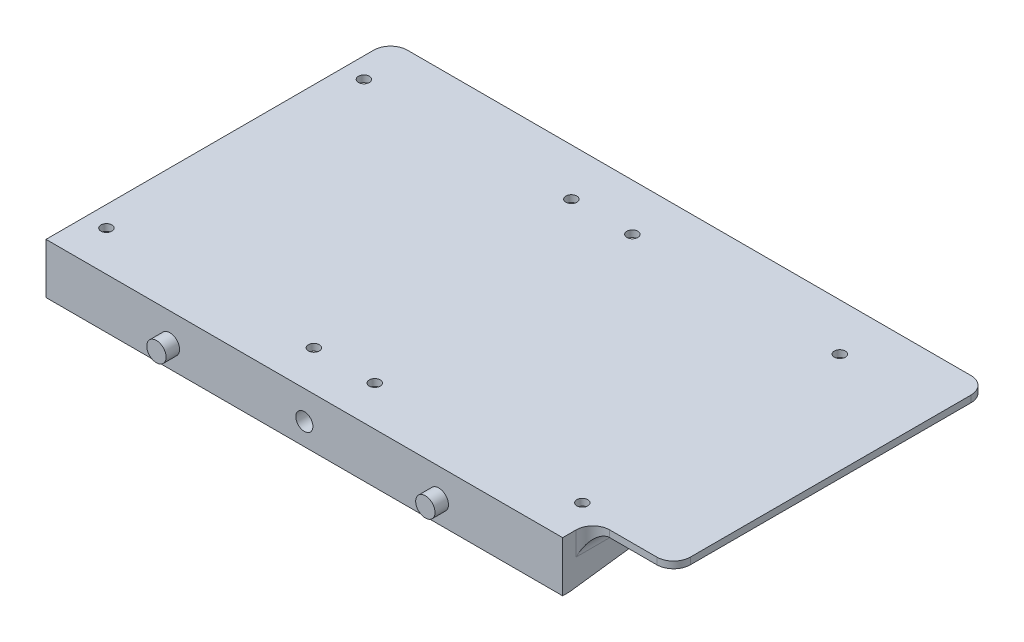
SolidWorks part; units mm, degrees
ref_plane "Front Plane" through (0, 0, 0) normal (0, 0, 1) x (1, 0, 0)
ref_plane "Top Plane" through (0, 0, 0) normal (0, 1, 0) x (1, 0, 0)
ref_plane "Right Plane" through (0, 0, 0) normal (1, 0, 0) x (0, 0, -1)
sketch "Sketch1" plane through (0, 0, 0) normal (0, 1, 0) x (1, 0, 0)
  line L0 (69.85, 0) -> (79.85, 0)
  line L1 (0, 0) -> (69.85, 0)
  line L2 (0, 0) -> (0, 100.5)
  line L3 (0, 100.5) -> (69.85, 100.5)
  line L4 (69.85, 0) -> (69.85, 100.5)
  line L5 (69.85, 100.5) -> (79.85, 100.5)
  line L6 (79.85, 0) -> (149.7, 0)
  line L7 (79.85, 0) -> (79.85, 100.5)
  line L8 (79.85, 100.5) -> (149.7, 100.5)
  line L9 (149.7, 0) -> (149.7, 100.5)
  line L10 (0, 100.5) -> (0, 86.5)
  line L11 (0, 86.5) -> (4.07, 86.5)
  line L12 (4.07, 86.5) -> (65.79, 86.5)
  line L13 (65.79, 86.5) -> (65.79, 9.9)
  line L14 (65.79, 9.9) -> (4.07, 9.9)
  circle A0 centre (4.07, 86.5) radius 1.625
  circle A1 centre (4.07, 9.9) radius 1.625
  circle A2 centre (65.79, 9.9) radius 1.625
  circle A3 centre (65.79, 86.5) radius 1.625
  circle A4 centre (145.64, 9.9) radius 1.625
  circle A5 centre (83.92, 9.9) radius 1.625
  circle A6 centre (83.92, 86.5) radius 1.625
  circle A7 centre (145.64, 86.5) radius 1.625
extrude "Boss-Extrude1" add sketch "Sketch1" along normal blind 2 contours A3 A2 A1 A0 L2 L1 L4 L3 | L0 L7 L5 L4 | L6 L9 L8 L7 A7 A6 A5 A4 region at (74.85, 0, -50.25) region at (34.925, 0, -50.2597) region at (114.775, 0, -50.2597)
ref_plane "Plane1" through (149.7, 0, 0) normal (1, 0, 0) x (0, 0, -1)
sketch "Sketch3" plane through (0, 0, 0) normal (0, 0, 1) x (1, 0, 0)
  line L0 (0, 2) -> (149.7, 2)
  line L1 (149.7, -41.1675) -> (149.7, 41.1675) construction
  line L2 (0, 2) -> (149.7, 2) construction
  line L3 (149.7, 2) -> (159.7, 2)
  line L4 (159.7, 2) -> (159.7, -13)
  line L5 (0, 2) -> (-10, 2)
  line L6 (-10, 2) -> (-10, -13)
  line L8 (-10, 2) -> (159.7, 2)
  line L9 (-10, 2) -> (-10, -13)
  line L10 (-10, -13) -> (159.7, -13)
  line L11 (159.7, 2) -> (159.7, -13)
  line M5 (0, 0) -> (149.7, 0)
  line M6 (149.7, 0) -> (149.7, 2)
  line M7 (149.7, 2) -> (0, 2)
  line M8 (0, 2) -> (0, 0)
extrude "Boss-Extrude2" add sketch "Sketch3" along normal blind 2 contours L6 L10 L4 L3 L5 M6 M5 M8 | M8 M5 M6 M7 region at (74.85, -6.3664, 0) region at (74.85, 1, 0)
sketch "Sketch4" plane through (0, 0, 0) normal (-1, 0, 0) x (0, 0, 1)
  line L0 (-100.5, 0) -> (0, -13)
  line L1 (0, -13) -> (0, 2)
  line L2 (0, 2) -> (-100.5, 2)
  line L7 (-100.5, 0) -> (0, 0)
  line L8 (0, 0) -> (0, 2)
  line L9 (0, 2) -> (-100.5, 2)
  line L10 (-100.5, 2) -> (-100.5, 0)
  line L11 (-100.5, 0) -> (0, 0)
  line L12 (0, 0) -> (0, 2)
  line L13 (0, 2) -> (-100.5, 2)
  line M1 (-100.5, 0) -> (0, 0)
  line M2 (0, 0) -> (0, 2)
  line M3 (0, 2) -> (-100.5, 2)
  line M4 (-100.5, 2) -> (-100.5, 0)
  dimension "D1" = 0
extrude "Boss-Extrude3" add sketch "Sketch4" along normal blind 2 contours L0 L1 M1 | M4 M1 M2 M3 region at (0, -4.3333, -33.5) region at (0, 1, -50.25)
sketch "Sketch5" plane through (149.7, 0, 0) normal (1, 0, 0) x (0, 0, -1)
  line L0 (100.5, 0) -> (0, -13)
  line L1 (0, -13) -> (0, 2)
  line L2 (0, 2) -> (100.5, 2)
  line L3 (100.5, 2) -> (100.5, 0)
extrude "Boss-Extrude4" add sketch "Sketch5" along normal blind 2
sketch "Sketch6" plane through (0, 0, 0) normal (0, 0, -1) x (-1, 0, 0)
  line L0 (10, 2) -> (2, 2) construction
  line L1 (2, 2) -> (2, -13) construction
  line L2 (2, -13) -> (10, -13) construction
  line L3 (10, -13) -> (10, 2) construction
  line L4 (-159.7, -13) -> (-151.7, -13) construction
  line L5 (-151.7, -13) -> (-151.7, 2) construction
  line L6 (-151.7, 2) -> (-159.7, 2) construction
  line L7 (-159.7, 2) -> (-159.7, -13) construction
  line L8 (10, 2) -> (2, 2)
  line L9 (2, 2) -> (2, -13)
  line L10 (2, -13) -> (10, -13)
  line L11 (10, -13) -> (10, 2)
  line L12 (-159.7, -13) -> (-151.7, -13)
  line L13 (-151.7, -13) -> (-151.7, 2)
  line L14 (-151.7, 2) -> (-159.7, 2)
  line L15 (-159.7, 2) -> (-159.7, -13)
extrude "Boss-Extrude5" add sketch "Sketch6" along normal blind 3
sketch "Sketch8" plane through (0, 0, -3) normal (0, 0, -1) x (-1, 0, 0)
  line L0 (-159.7, 2) -> (-159.7, -13)
  line L1 (-159.7, -5.5) -> (-151.7, -5.5)
  line L2 (-151.7, -12.6119) -> (-151.7, 2) construction
  line L3 (10, -5.5) -> (2, -5.5)
  line L4 (10, -13) -> (10, 2) construction
  line L5 (2, 2) -> (2, -12.6119) construction
  circle A0 centre (-155.7, -5.5) radius 2.55
  circle A1 centre (6, -5.5) radius 2.55
extrude "Cut-Extrude1" cut sketch "Sketch8" against normal blind 10 contours L1 A0 | L1 A0 | L3 A1 | L3 A1 region at (155.7, -4.4177, -3) region at (155.7, -6.5823, -3) region at (-6, -6.5823, -3) region at (-6, -4.4177, -3)
fillet "Fillet1" radius 3 4 edges at (159.7, -13, -0.5) (159.7, 2, -0.5) (-10, -13, -0.5) (-10, 2, -0.5)
sketch "Sketch9" plane through (0, 0, 0) normal (0, 0, -1) x (-1, 0, 0)
  line L0 (-74.85, 0) -> (-74.85, -13)
  line L1 (0, 0) -> (-149.7, 0) construction
  line L2 (0, -13) -> (-149.7, -13) construction
  circle A0 centre (-74.85, -6.5) radius 2.55
extrude "Cut-Extrude2" cut sketch "Sketch9" against normal blind 10 contours L0 A0 | L0 A0 region at (73.7677, -6.5, 0) region at (75.9323, -6.5, 0)
sketch "Sketch10" plane through (0, 0, 0) normal (0, 0, -1) x (-1, 0, 0)
  circle A0 centre (-74.85, -6.5) radius 4
  circle A1 centre (-74.85, -6.5) radius 2.55
extrude "Boss-Extrude6" add sketch "Sketch10" along normal blind 3
sketch "Sketch12" plane through (0, 0, 2) normal (0, 0, 1) x (1, 0, 0)
  line L0 (74.85, -6.5) -> (34.85, -6.5)
  line L1 (34.85, -6.5) -> (114.85, -6.5)
  circle A0 centre (34.85, -6.5) radius 2.875
  circle A1 centre (114.85, -6.5) radius 2.875
extrude "Boss-Extrude7" add sketch "Sketch12" along normal blind 4 contours A1 | A0 region at (114.85, -3.7063, 2)
sketch "Sketch13" plane through (0, 0, -3) normal (0, 0, -1) x (-1, 0, 0)
  line L1 (-151.7, 2) -> (-162.6469, 2)
  line L2 (-151.7, 2) -> (-151.7, -15.5804)
  line L3 (-151.7, -15.5804) -> (-162.6469, -15.5804)
  line L4 (-162.6469, 2) -> (-162.6469, -15.5804)
  line L5 (2, 2) -> (12.2965, 2)
  line L6 (2, 2) -> (2, -21.4335)
  line L7 (2, -21.4335) -> (12.2965, -21.4335)
  line L8 (12.2965, 2) -> (12.2965, -21.4335)
extrude "Cut-Extrude3" cut sketch "Sketch13" against normal blind 43
sketch "Sketch15" plane through (0, 2, 0) normal (0, 1, 0) x (1, 0, 0)
  line L0 (151.7, -2) -> (151.7, 7)
  line L1 (151.7, 100.5) -> (151.7, -2) construction
  line L2 (151.7, 7) -> (175.7, 7)
  line L3 (175.7, 7) -> (175.7, 100.5)
  line L4 (175.7, 100.5) -> (151.7, 100.5)
  line L9 (-2, -2) -> (151.7, -2)
  line L10 (151.7, -2) -> (151.7, 100.5)
  line L11 (151.7, 100.5) -> (-2, 100.5)
  line L12 (-2, 100.5) -> (-2, -2)
  line L14 (151.7, -2) -> (151.7, 100.5)
  line M2 (151.7, -2) -> (151.7, 100.5)
  dimension "D1" = 0
extrude "Boss-Extrude8" add sketch "Sketch15" against normal up to surface (2 mm away) contours L3 L4 L2 M2 region at (163.7, 2, -53.75) up to face at (65.79, 0, -8.275)
fillet "Fillet2" radius 5 4 edges at (151.7, 1, -7) (175.7, 1, -7) (-2, 1, -100.5) (175.7, 1, -100.5)
fillet "Fillet3" radius 5 1 edges at (151.7, 0, -51.25)
